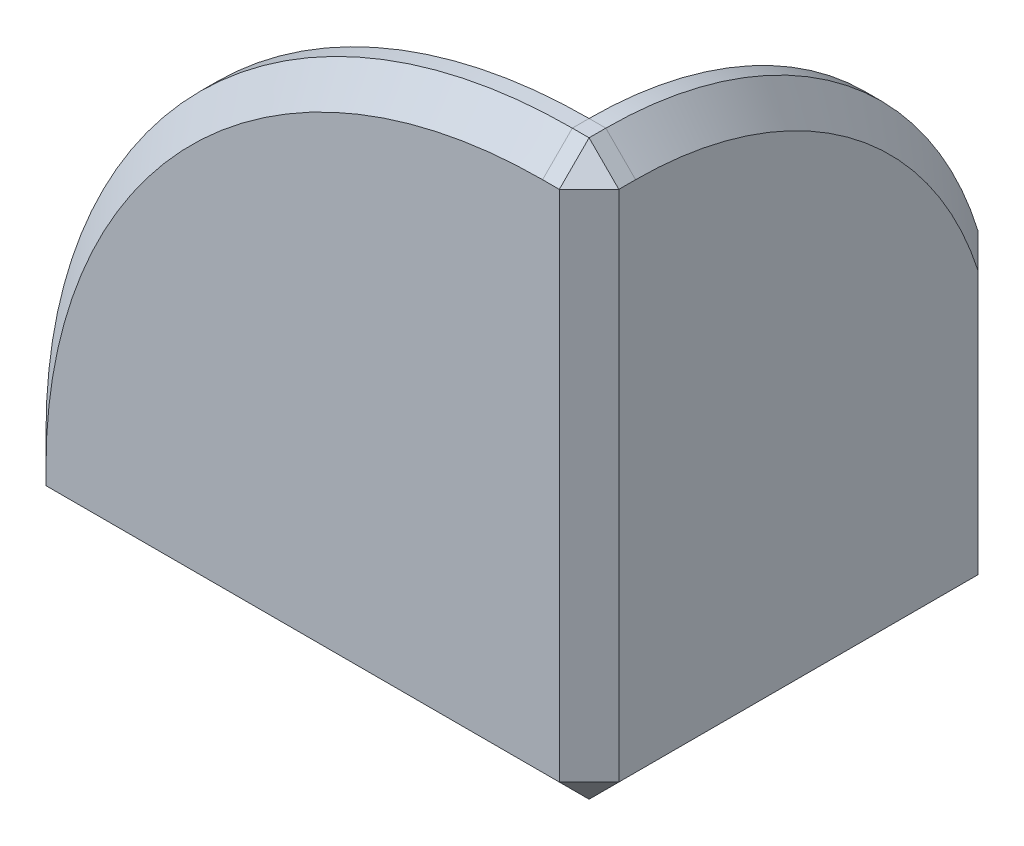
SolidWorks part; units mm, degrees
ref_plane "Front Plane" through (0, 0, 0) normal (0, 0, 1) x (1, 0, 0)
ref_plane "Top Plane" through (0, 0, 0) normal (0, 1, 0) x (1, 0, 0)
ref_plane "Right Plane" through (0, 0, 0) normal (1, 0, 0) x (0, 0, -1)
sketch "Sketch1" plane through (0, 0, 0) normal (0, 0, 1) x (1, 0, 0)
  line L0 (0, 0) -> (0, 35.921)
  line L1 (0, 25.4) -> (-25.4, 25.4) construction
  line L2 (-25.4, 25.4) -> (-25.4, 0) construction
  line L3 (0, 0) -> (-35.921, 0)
  arc A0 (0, 35.921) -> (-35.921, 0) centre (0, 0) ccw
  dimension "D1" = 25.4
  dimension "D2" = 25.4
extrude "Boss-Extrude1" add sketch "Sketch1" along normal blind 3.175
sketch "Sketch2" plane through (0, 0, 0) normal (1, 0, 0) x (0, 0, -1)
  line L0 (0, 0) -> (25.4, 0)
  line L1 (25.4, 0) -> (25.4, 17.145)
  line L2 (-3.175, 35.921) -> (0, 35.921) construction
  line L3 (0, 35.921) -> (-3.175, 35.921)
  line L4 (-3.175, 35.921) -> (-3.175, 0)
  line L5 (-3.175, 0) -> (0, 0)
  arc A0 (0, 35.921) -> (25.4, 17.145) centre (0, 9.3526) cw
  dimension "D1" = 25.4
  dimension "D2" = 17.145
extrude "Boss-Extrude2" add sketch "Sketch2" along normal blind 3.175
sketch "Sketch3" plane through (0, 0, 0) normal (0, -1, 0) x (1, 0, 0)
  line L0 (0, -25.4) -> (-17.145, -25.4)
  line L1 (0, -25.4) -> (3.175, -25.4)
  line L2 (3.175, -25.4) -> (3.175, 3.175)
  line L3 (3.175, 3.175) -> (-35.921, 3.175)
  line L4 (-35.921, 3.175) -> (-35.921, 0)
  arc A0 (-35.921, 0) -> (-17.145, -25.4) centre (-9.3526, 0) ccw
  dimension "D1" = 17.145
extrude "Boss-Extrude3" add sketch "Sketch3" along normal blind 3.175
chamfer "Chamfer1" distance 2.032 angle 45 12 edges at (-30.7174, -3.175, -15.7932) (-35.921, -3.175, 1.5875) (-6.985, -3.175, -25.4) (3.175, 35.921, 1.5875) (3.175, 30.7174, -15.7932) (3.175, 6.985, -25.4) (3.175, -3.175, -11.1125) (1.5875, 35.921, 3.175) (3.175, 16.373, 3.175) (-16.373, -3.175, 3.175) (-35.921, -1.5875, 3.175) (-25.4, 25.4, 3.175)
